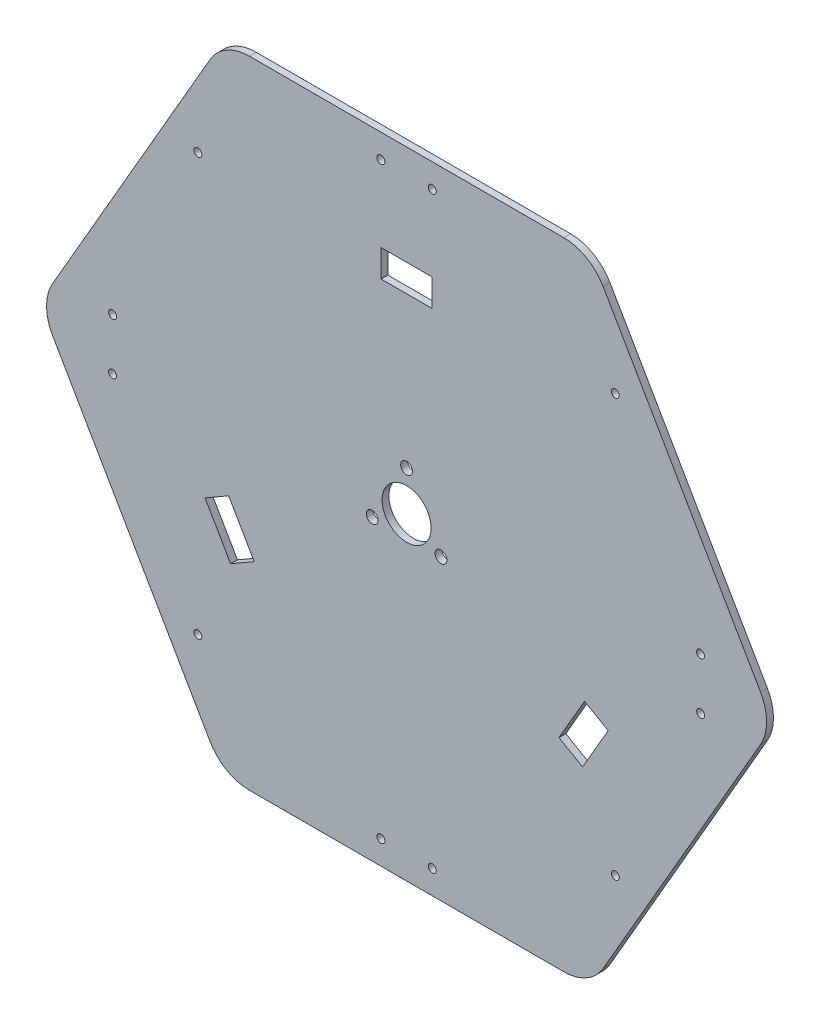
SolidWorks part; units mm, degrees
ref_plane "Alzado" through (0, 0, 0) normal (0, 0, 1) x (1, 0, 0)
ref_plane "Planta" through (0, 0, 0) normal (0, 1, 0) x (1, 0, 0)
ref_plane "Vista lateral" through (0, 0, 0) normal (1, 0, 0) x (0, 0, -1)
sketch "Croquis1" plane through (0, 0, 0) normal (0, 0, 1) x (1, 0, 0)
  line L0 (11.25, 96) -> (-11.25, 84) construction
  line L1 (-11.25, 96) -> (11.25, 96)
  line L2 (-11.25, 96) -> (-11.25, 84)
  line L3 (-11.25, 84) -> (11.25, 84)
  line L4 (11.25, 96) -> (11.25, 84)
  line L5 (-11.25, 96) -> (11.25, 84) construction
  line L6 (88.7634, -38.2572) -> (78.3711, -32.2572)
  line L7 (88.7634, -38.2572) -> (77.5134, -57.7428)
  line L8 (77.5134, -57.7428) -> (67.1211, -51.7428)
  line L9 (78.3711, -32.2572) -> (67.1211, -51.7428)
  line L10 (-77.5134, -57.7428) -> (-67.1211, -51.7428)
  line L11 (-77.5134, -57.7428) -> (-88.7634, -38.2572)
  line L12 (-88.7634, -38.2572) -> (-78.3711, -32.2572)
  line L13 (-67.1211, -51.7428) -> (-78.3711, -32.2572)
  line L14 (0, -0.7536) -> (0, 0) construction
  line L15 (0, 0) -> (0, 17.5) construction
  line L17 (-80.829, -140) -> (80.829, -140)
  line L18 (80.829, -140) -> (161.6581, 0)
  line L19 (161.6581, 0) -> (80.829, 140)
  line L20 (80.829, 140) -> (-80.829, 140)
  line L21 (-80.829, 140) -> (-161.6581, 0)
  line L22 (-161.6581, 0) -> (-80.829, -140)
  circle A0 centre (0, 0) radius 150
  circle A1 centre (0, 0) radius 10.8
  circle A2 centre (0, 0) radius 90 construction
  circle A3 centre (0, 90) radius 40 construction
  circle A4 centre (77.9423, -45) radius 40 construction
  circle A5 centre (-77.9423, -45) radius 40 construction
  circle A6 centre (0, 0) radius 17.5 construction
  circle A7 centre (0, 17.5) radius 2.6
  circle A8 centre (0, 0) radius 140 construction
  circle A9 centre (15.1554, -8.75) radius 2.6
  circle A10 centre (-15.1554, -8.75) radius 2.6
  point P11 (0, 90)
  point P18 (0, 0)
  point P28 (0, 0)
  point P39 (0, 0)
  dimension "D1" = 300
  dimension "D2" = 21.6
  dimension "D3" = 180
  dimension "D4" = 80
  dimension "D9" = 5.2
  dimension "D10" = 3
  dimension "D11" = 50
  dimension "D5" = 12
  dimension "D6" = 22.5
  dimension "D7" = 3
  dimension "D8" = 3
extrude "Saliente-Extruir1" add sketch "Croquis1" along normal blind 3 contours L19 A0 L20 L21 L22 L17 L18 A10 A9 A7 A1 L1 L4 L3 L2 L9 L6 L7 L8 L13 L10 L11 L12 | A0 L20 L21 | A0 L19 L20 | A0 L18 L19 | A0 L17 L18 | A0 L22 L17 | A0 L21 L22 region at (-76.7492, -132.9335, 0) region at (-72.9482, -126.3499, 0) region at (76.7492, -132.9335, 0) region at (-153.4984, 0, 0) region at (153.4984, 0, 0) region at (-76.7492, 132.9335, 0) region at (76.7492, 132.9335, 0)
fillet "Redondeo1" radius 20 6 edges at (80.829, 140, 1.5) (-80.829, 140, 1.5) (-161.6581, 0, 1.5) (-80.829, -140, 1.5) (80.829, -140, 1.5) (161.6581, 0, 1.5)
sketch "Croquis2" plane through (0, 0, 0) normal (0, 0, -1) x (-1, 0, 0)
  circle A0 centre (0, 0) radius 102.5 construction
  circle A1 centre (0, 0) radius 140 construction
  dimension "D1" = 280
  dimension "D2" = 205
sketch "Croquis3" plane through (0, 0, 0) normal (0, 0, -1) x (1, 0, 0)
  circle A0 centre (129.5053, 11.3302) radius 1.75
  circle A1 centre (91.9239, 91.9239) radius 1.75
  circle A2 centre (11.3302, 129.5053) radius 1.75
extrude "Cortar-Extruir1" cut sketch "Croquis3" against normal through all
pattern_circular "MatrizC1" count 4 over 360 about axis through (0, 0, 0) along (0, 0, 1) of "Cortar-Extruir1"
